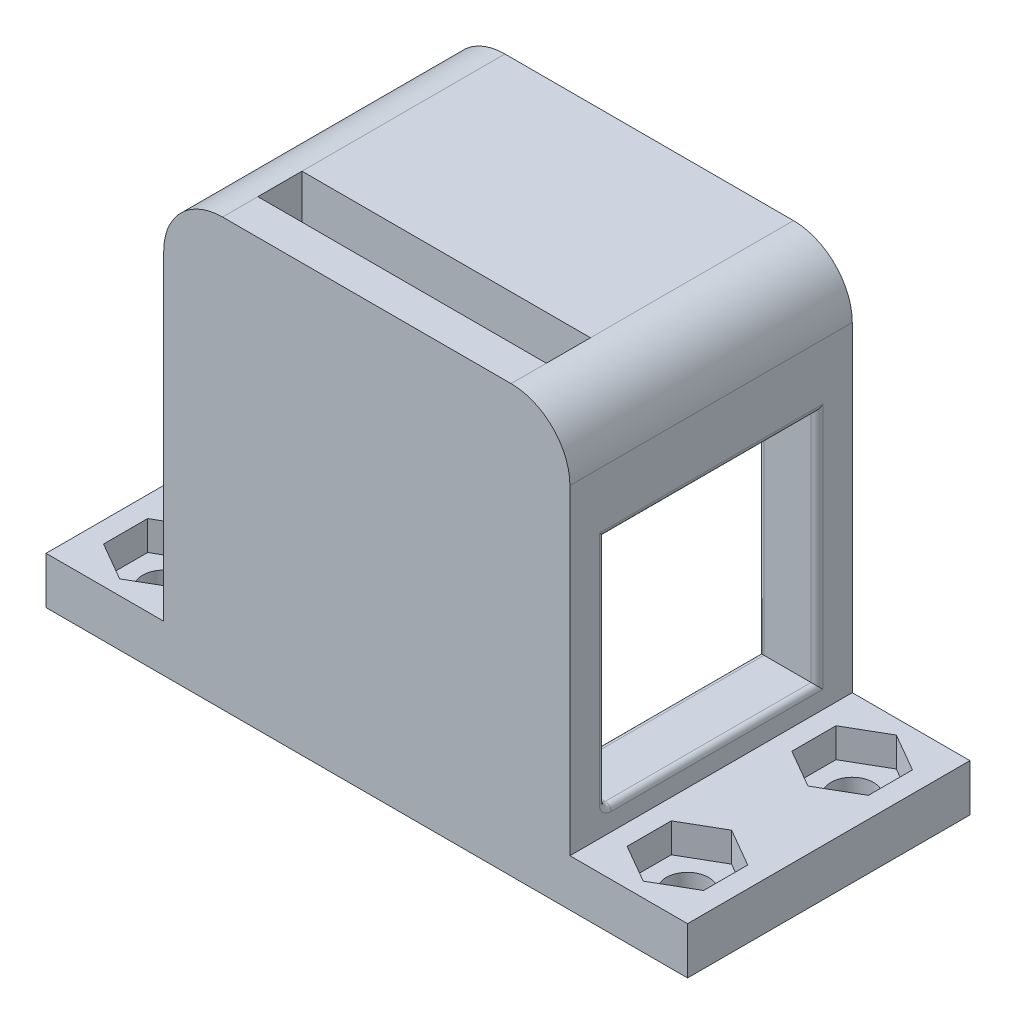
SolidWorks part; units mm, degrees
ref_plane "Front Plane" through (0, 0, 0) normal (0, 0, 1) x (1, 0, 0)
ref_plane "Top Plane" through (0, 0, 0) normal (0, 1, 0) x (1, 0, 0)
ref_plane "Right Plane" through (0, 0, 0) normal (1, 0, 0) x (0, 0, -1)
sketch "Sketch1" plane through (0, 0, 0) normal (0, 0, 1) x (1, 0, 0)
  line L1 (-27.2601, 4.8) -> (-12.2601, 4.8)
  line L2 (-27.2601, 4.8) -> (-27.2601, 8.8)
  line L3 (-27.2601, 8.8) -> (-17.2601, 8.8)
  line L6 (-12.2601, 4.8) -> (-12.2601, 36.5)
  line L8 (-17.2601, 8.8) -> (-17.2601, 39.5587)
  line L9 (-12, 41.05) -> (12, 41.05)
  line L11 (-12.2601, 36.5) -> (12.2601, 36.5)
  line L14 (17.2601, 8.8) -> (17.2601, 38.3587)
  line L15 (12, 41.05) -> (15.1507, 41.05)
  line L16 (12.2601, 4.8) -> (12.2601, 36.5)
  line L18 (27.2601, 8.8) -> (17.2601, 8.8)
  line L19 (27.2601, 4.8) -> (27.2601, 8.8)
  line L20 (27.2601, 4.8) -> (12.2601, 4.8)
  line L21 (-17.2601, 39.5587) -> (-17.2601, 41.05)
  line L22 (-17.2601, 41.05) -> (-12, 41.05)
  line L23 (15.1507, 41.05) -> (17.2601, 41.05)
  line L25 (17.2601, 41.05) -> (17.2601, 38.3587)
  point P4 (0, 36.5)
  dimension "D2" = 5
  dimension "D3" = 10
  dimension "D6" = 4.55
  dimension "D8" = 24.5203
  dimension "D9" = 31.7
  dimension "D10" = 4
  dimension "D11" = 4
extrude "Boss-Extrude1" add sketch "Sketch1" along normal blind 17.5
sketch "Sketch2" plane through (0, 0, 17.5) normal (0, 0, 1) x (1, 0, 0)
  line L0 (-17.2601, 8.8) -> (-17.2601, 41.05)
  line L1 (-17.2601, 41.05) -> (17.2601, 41.05)
  line L2 (17.2601, 41.05) -> (17.2601, 4.8)
  line L3 (12.2601, 4.8) -> (27.2601, 4.8) construction
  line L4 (17.2601, 4.8) -> (-17.2601, 4.8)
  line L5 (-27.2601, 4.8) -> (-12.2601, 4.8) construction
  line L6 (-17.2601, 4.8) -> (-17.2601, 8.8)
extrude "Boss-Extrude2" add sketch "Sketch2" along normal blind 6.5
sketch "Sketch4" plane through (0, 0, 17.5) normal (0, 0, -1) x (-1, 0, 0)
  line L1 (-12.2601, 36.5) -> (12.2601, 36.5)
  line L2 (-12.2601, 36.5) -> (-12.2601, 4.8)
  line L3 (-12.2601, 4.8) -> (12.2601, 4.8)
  line L4 (12.2601, 36.5) -> (12.2601, 4.8)
extrude "Cut-Extrude1" cut sketch "Sketch4" against normal blind 3.5
sketch "Sketch5" plane through (0, 0, 21) normal (0, 0, -1) x (-1, 0, 0)
  line L0 (-17.2601, 41.05) -> (17.2601, 41.05) construction
  line L1 (-12.2601, 36.5) -> (-14.9466, 36.5)
  line L2 (-12.2601, 36.5) -> (-12.2601, 38.5)
  line L3 (-12.2601, 38.5) -> (-14.9466, 38.5)
  line L4 (-14.9466, 36.5) -> (-14.9466, 38.5)
  dimension "D1" = 2.55
extrude "Cut-Extrude2" [suppressed] cut sketch "Sketch5" along normal blind 4.5
fillet "Fillet1" radius 5 2 edges at (-17.2601, 41.05, 12) (17.2601, 41.05, 12)
sketch "Sketch7" plane through (0, 0, 17.5) normal (0, 0, 1) x (1, 0, 0)
  line L1 (-27.2601, 8.8) -> (-17.2601, 8.8)
  line L2 (-27.2601, 8.8) -> (-27.2601, 4.8)
  line L3 (-27.2601, 4.8) -> (-17.2601, 4.8)
  line L4 (-17.2601, 8.8) -> (-17.2601, 4.8)
  line L5 (17.2601, 8.8) -> (27.2601, 8.8)
  line L6 (17.2601, 8.8) -> (17.2601, 4.8)
  line L7 (17.2601, 4.8) -> (27.2601, 4.8)
  line L8 (27.2601, 8.8) -> (27.2601, 4.8)
extrude "Boss-Extrude3" add sketch "Sketch7" along normal through all
sketch "Sketch6" plane through (0, 8.8, 0) normal (0, 1, 0) x (1, 0, 0)
  line L0 (27.2601, -24) -> (27.2601, 0) construction
  line L40 (22.25, -1.2472) -> (25.5, -3.1236)
  line L45 (92.1046, -12) -> (-37.5844, -12) construction
  line L47 (19, -3.1236) -> (22.25, -1.2472)
  line L48 (19, -6.8764) -> (19, -3.1236)
  line L49 (22.25, -8.7528) -> (19, -6.8764)
  line L56 (25.5, -6.8764) -> (22.25, -8.7528)
  line L65 (25.5, -3.1236) -> (25.5, -6.8764)
  line L66 (22.25, -22.7528) -> (25.5, -20.8764)
  line L67 (25.5, -20.8764) -> (25.5, -17.1236)
  line L68 (25.5, -17.1236) -> (22.25, -15.2472)
  line L69 (22.25, -15.2472) -> (19, -17.1236)
  line L70 (19, -17.1236) -> (19, -20.8764)
  line L71 (19, -20.8764) -> (22.25, -22.7528)
  line L72 (0, -59.0369) -> (0, -80.7994) construction
  line L74 (0, -55) -> (0, 55) construction
  line L75 (-22.25, -8.7528) -> (-19, -6.8764)
  line L76 (-19, -6.8764) -> (-19, -3.1236)
  line L77 (-19, -3.1236) -> (-22.25, -1.2472)
  line L78 (-22.25, -1.2472) -> (-25.5, -3.1236)
  line L79 (-25.5, -3.1236) -> (-25.5, -6.8764)
  line L80 (-25.5, -6.8764) -> (-22.25, -8.7528)
  line L81 (-22.25, -15.2472) -> (-19, -17.1236)
  line L82 (-19, -17.1236) -> (-19, -20.8764)
  line L83 (-19, -20.8764) -> (-22.25, -22.7528)
  line L84 (-22.25, -22.7528) -> (-25.5, -20.8764)
  line L85 (-25.5, -20.8764) -> (-25.5, -17.1236)
  line L86 (-25.5, -17.1236) -> (-22.25, -15.2472)
  circle A4 centre (22.25, -19) radius 3.25 construction
  point P4 (27.2601, -12)
  point P12 (20.625, -16.1854)
  point P34 (-20.625, -16.1854)
  dimension "D1" = 22.25
  dimension "D4" = 6.5
  dimension "D2" = 7
fillet "Fillet2" radius 1 2 edges at (12.2601, 20.65, 0) (-12.2601, 20.65, 0)
sketch "Sketch8" plane through (-17.2601, 0, 0) normal (-1, 0, 0) x (0, 0, 1)
  line L0 (24, 36.05) -> (24, 8.8) construction
  line L1 (3, 30.8) -> (21, 30.8)
  line L2 (3, 30.8) -> (3, 10.8)
  line L3 (3, 10.8) -> (21, 10.8)
  line L4 (21, 30.8) -> (21, 10.8)
  line L6 (24, 8.8) -> (0, 8.8) construction
  dimension "D1" = 18
  dimension "D2" = 20
  dimension "D3" = 3
  dimension "D4" = 2
extrude "Cut-Extrude4" cut sketch "Sketch8" against normal through all
fillet "Fillet3" radius 0.5 16 edges at (-14.7601, 10.8, 21) (-17.2601, 10.8, 12) (-17.2601, 20.8, 3) (-17.2601, 20.8, 21) (-17.2601, 30.8, 12) (-12.2601, 10.8, 12) (-12.2601, 20.8, 3) (-12.2601, 7.8, 21) (12.2601, 7.8, 21) (17.2601, 10.8, 12) (12.2601, 20.8, 3) (12.2601, 10.8, 12) (17.2601, 30.8, 12) (17.2601, 20.8, 3) (17.2601, 20.8, 21) (14.7601, 10.8, 21)
extrude "Cut-Extrude7" cut sketch "Sketch6" against normal offset from surface (2.5 mm away) 1.5 up to face at (0, 4.8, 11.0661)
sketch "Sketch11" plane through (0, 8.8, 0) normal (0, 1, 0) x (1, 0, 0)
  line L0 (22.25, -22.7528) -> (25.5, -20.8764) construction
  line L1 (25.5, -17.1236) -> (22.25, -15.2472) construction
  line L2 (19, -17.1236) -> (19, -20.8764) construction
  line L3 (22.25, -8.7528) -> (25.5, -6.8764) construction
  line L4 (25.5, -3.1236) -> (22.25, -1.2472) construction
  line L5 (19, -3.1236) -> (19, -6.8764) construction
  line L6 (-22.25, -22.7528) -> (-19, -20.8764) construction
  line L7 (-25.5, -17.1236) -> (-25.5, -20.8764) construction
  line L8 (-19, -17.1236) -> (-22.25, -15.2472) construction
  line L9 (-22.25, -8.7528) -> (-19, -6.8764) construction
  line L10 (-19, -3.1236) -> (-22.25, -1.2472) construction
  line L11 (-25.5, -3.1236) -> (-25.5, -6.8764) construction
  circle A0 centre (22.25, -19) radius 3.25
  circle A1 centre (22.25, -5) radius 3.25
  circle A2 centre (-22.25, -5) radius 3.25
  circle A3 centre (-22.25, -19) radius 3.25
hole_wizard "M3 Clearance Hole1" positions "Sketch12" profile "Sketch13" hole size "M3" standard "ANSI Metric" end condition through all
sketch "Sketch12" plane through (0, 8.8, 0) normal (0, 1, 0) x (1, 0, 0)
  point P0 (22.25, -19)
  point P3 (22.25, -5)
  point P6 (-22.25, -5)
  point P9 (-22.25, -19)
sketch "Sketch13" plane through (22.25, 8.8, 19) normal (1, 0, 0) x (0, 0, 1)
  line L0 (0, 0) -> (0, 4)
  line L1 (0, 4) -> (1.8, 4)
  line L2 (1.8, 4) -> (1.8, 0)
  line L5 (1.8, 0) -> (0, 0)
  line L11 (0, -6.35) -> (0, 107.95) construction
  dimension "Thru Hole Dia." = 3.6
  dimension "Thru Hole Depth" = 4
sketch "Sketch14" plane through (0, 36.5, 0) normal (0, -1, 0) x (1, 0, 0)
  line L0 (-12.2601, 21) -> (12.2601, 21) construction
  line L1 (12.2601, 17.25) -> (-12.2601, 17.25)
  line L2 (12.2601, 17.25) -> (12.2601, 21)
  line L3 (12.2601, 21) -> (-12.2601, 21)
  line L4 (-12.2601, 17.25) -> (-12.2601, 21)
  line L5 (-12.2601, 21) -> (-12.2601, 1) construction
  line L6 (12.2601, 21) -> (12.2601, 1) construction
  dimension "D1" = 3.75
extrude "Cut-Extrude8" cut sketch "Sketch14" against normal through all
